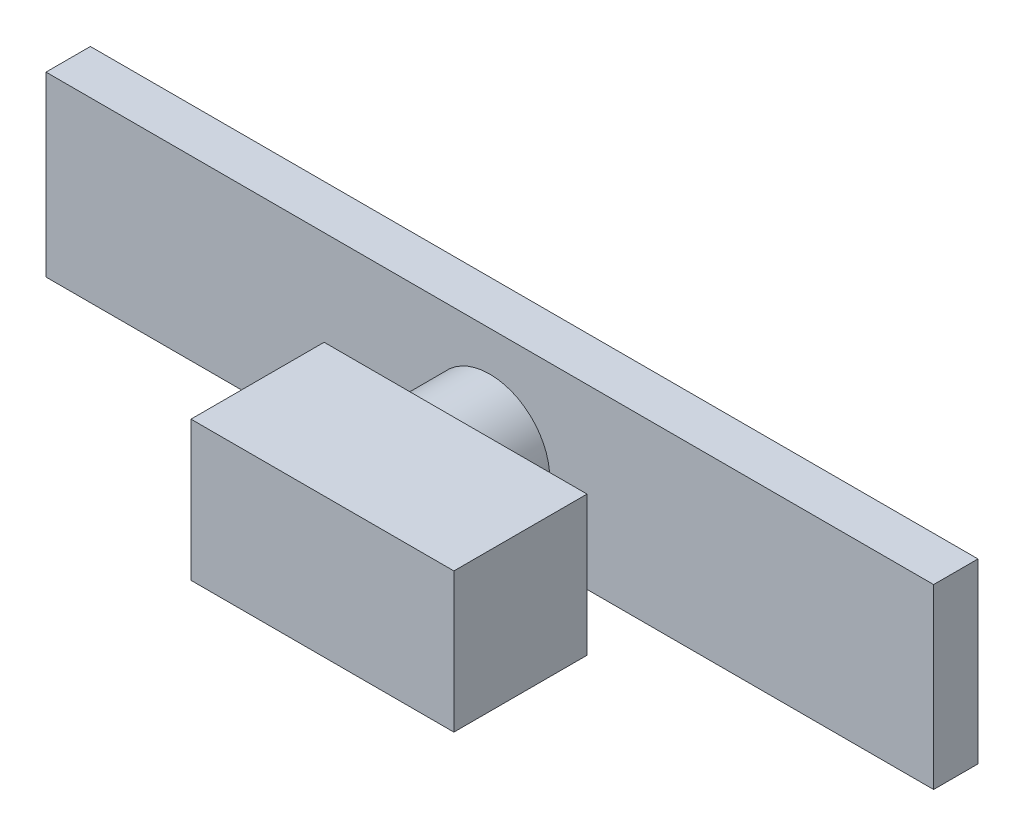
SolidWorks part; units mm, degrees
ref_plane "Front Plane" through (0, 0, 0) normal (0, 0, 1) x (1, 0, 0)
ref_plane "Top Plane" through (0, 0, 0) normal (0, 1, 0) x (1, 0, 0)
ref_plane "Right Plane" through (0, 0, 0) normal (1, 0, 0) x (0, 0, -1)
sketch "Sketch2" plane through (0, 0, 0) normal (0, 0, 1) x (1, 0, 0)
  line L1 (-47.8692, 21.2481) -> (206.1308, 21.2481)
  line L2 (-47.8692, 21.2481) -> (-47.8692, 8.5481)
  line L3 (-47.8692, 8.5481) -> (206.1308, 8.5481)
  line L4 (206.1308, 21.2481) -> (206.1308, 8.5481)
  dimension "D1" = 12.7
  dimension "D2" = 254
extrude "Boss-Extrude1" add sketch "Sketch2" along normal blind 50.8
sketch "Sketch3" plane through (0, 21.2481, 0) normal (0, 1, 0) x (1, 0, 0)
  circle A0 centre (79.1308, -28.4831) radius 17.1408
extrude "Boss-Extrude2" add sketch "Sketch3" along normal blind 19.05
sketch "Sketch4" plane through (0, 40.2981, 0) normal (0, 1, 0) x (1, 0, 0)
  line L1 (50.7675, -8.111) -> (126.0034, -8.111)
  line L2 (50.7675, -8.111) -> (50.7675, -48.0661)
  line L3 (50.7675, -48.0661) -> (126.0034, -48.0661)
  line L4 (126.0034, -8.111) -> (126.0034, -48.0661)
extrude "Boss-Extrude3" add sketch "Sketch4" along normal blind 38.1
scale "Scale2" scale about centroid uniform scaling yes scale factor 0.06
move or copy body "Body-Move/Copy1" bodies to move or copy 105 copy no rotation origin (0, 33.6669, 26.5501) rotation axis (1, 0, 0) rotation angle 90
move or copy body "Body-Move/Copy3" bodies to move or copy 106 copy no translate (-50.8, 0, -50.8)
scale "Scale5" scale about centroid uniform scaling yes scale factor 0.25
